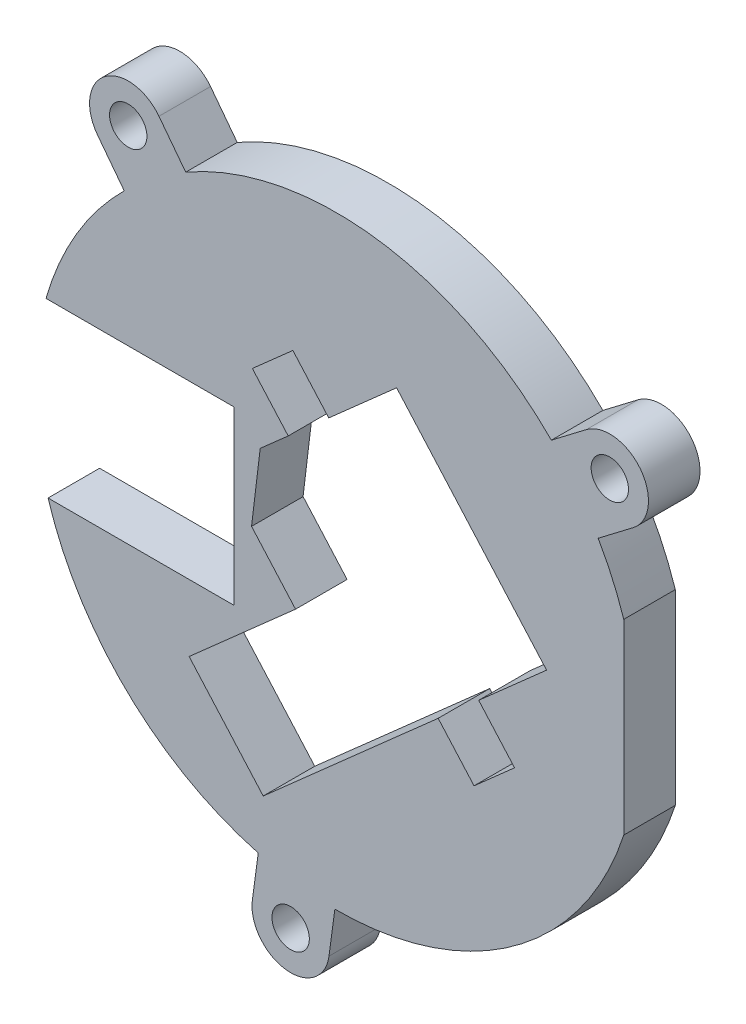
SolidWorks part; units mm, degrees
ref_plane "Front Plane" through (0, 0, 0) normal (0, 0, 1) x (1, 0, 0)
ref_plane "Top Plane" through (0, 0, 0) normal (0, 1, 0) x (1, 0, 0)
ref_plane "Right Plane" through (0, 0, 0) normal (1, 0, 0) x (0, 0, -1)
sketch "Sketch1" plane through (0, 0, 0) normal (0, 0, 1) x (1, 0, 0)
  line L0 (-21.141, 18.2245) -> (20.1141, 18.2245) construction
  line L1 (-4.8006, 1.8415) -> (-4.8006, -3.0861)
  line L2 (-4.8006, -3.0861) -> (-8.9662, -3.0861)
  line L3 (-8.9662, -3.0861) -> (-8.9662, -5.3514)
  line L4 (-8.9662, -5.3514) -> (-6.5786, -5.3514)
  line L5 (-4.9806, 7.3918) -> (-2.5835, 9.5123)
  line L6 (-2.5835, 9.5123) -> (-0.463, 7.1152)
  line L7 (-4.9806, 7.3918) -> (-2.8601, 4.9947)
  line L8 (3.2088, 10.3632) -> (-4.5153, 3.5306)
  line L9 (12.0777, 0.3371) -> (4.3536, -6.4955)
  line L10 (-4.5153, 3.5306) -> (-5.0276, -0.7207)
  line L11 (-5.0276, -0.7207) -> (0.0716, -6.4852)
  line L12 (0.0716, -6.4852) -> (4.3536, -6.4955)
  line L13 (-2.478, -3.6029) -> (7.6432, 5.3502) construction
  line L14 (3.2088, 10.3632) -> (12.0777, 0.3371)
  line L15 (3.2088, 10.3632) -> (11.8761, 18.0302)
  line L16 (-9.2588, -8.622) -> (-4.7522, -4.6355) construction
  line L17 (-9.2588, -8.622) -> (-5.994, -12.3128) construction
  line L18 (-4.7522, -4.6355) -> (-1.4874, -8.3263) construction
  line L19 (-5.994, -12.3128) -> (-1.4874, -8.3263) construction
  line L20 (12.0777, 0.3371) -> (20.228, 7.5468)
  line L21 (-6.5786, -5.3514) -> (-6.5786, -5.8039)
  line L22 (-6.5786, -5.8039) -> (-14.0208, -5.8039)
  line L23 (-14.0208, -5.8039) -> (-14.0208, 4.5593)
  line L24 (-14.0208, 4.5593) -> (-6.5786, 4.5593)
  line L25 (-6.5786, 4.5593) -> (-6.5786, 3.9924)
  line L26 (-6.5786, 3.9924) -> (-8.9662, 3.9924)
  line L27 (-8.9662, 3.9924) -> (-8.9662, 1.8415)
  line L28 (-8.9662, 1.8415) -> (-4.8006, 1.8415)
  line L29 (8.4059, -2.9109) -> (10.5264, -5.308)
  line L30 (10.5264, -5.308) -> (8.1292, -7.4285)
  line L31 (8.1292, -7.4285) -> (6.0088, -5.0313)
  line L32 (-4.7522, -4.6355) -> (-2.9639, -3.0536) construction
  line L33 (-1.4874, -8.3263) -> (0.5926, -6.4864) construction
  line L34 (-5.4555, -12.9216) -> (-0.9489, -8.9351)
  line L35 (-8.7203, -9.2308) -> (-4.2137, -5.2443)
  line L36 (-8.7203, -9.2308) -> (-5.4555, -12.9216)
  line L37 (-0.9489, -8.9351) -> (1.816, -6.4894)
  line L38 (-4.2137, -5.2443) -> (-2.4254, -3.6624)
  arc A0 (-15.2315, -0.5079) -> (3.302, 14.878) centre (0, 0) ccw construction
  circle A1 centre (0, 0) radius 21.59 construction
  circle A2 centre (0, 0) radius 21.59
  circle A3 centre (0, -18.415) radius 1.4224 construction
  circle A4 centre (0, 18.415) radius 1.4224 construction
  circle A5 centre (0, -18.415) radius 1.4224
  circle A6 centre (0, 18.415) radius 1.4224
  circle A7 centre (0, 0) radius 15.24
  dimension "D3" = 30.48
  dimension "D1" = 33.4645
  dimension "D2" = 20.0406
  dimension "D4" = 4.9276
  dimension "D5" = 2.7178
  dimension "D6" = 8.7122
  dimension "D7" = 7.8613
  dimension "D8" = 2.7178
  dimension "D9" = 3.2004
  dimension "D10" = 13.3858
  dimension "D11" = 3.1623
  dimension "D12" = 10.3124
  dimension "D13" = 8.6106
  dimension "D14" = 7.6962
  dimension "D15" = 6.0168
  dimension "D16" = 2.3876
  dimension "D17" = 4.9276
  dimension "D18" = 22.86
  dimension "D19" = 7.4422
  dimension "D20" = 5.0546
  dimension "D21" = 13.6652
  dimension "D22" = 29.2608
  dimension "D23" = 0.8128
extrude "Boss-Extrude1" add sketch "Sketch1" along normal blind 3.048 contours L15 A7 L20 L9 L29 L30 L31 L12 L33 L19 L17 L16 L32 L11 L1 L2 L3 L4 L21 L22 L23 L24 L25 L26 L27 L28 L10 L8 L7 L5 L6 | L28 L27 L26 L25 L24 L23 L22 L21 L4 L3 L2 L1 L11 L10 | A7 L15 A2 L20 A6 A5 region at (-6.8834, 2.2726, 0) region at (-10.1343, -0.6067, 0) region at (-13.5004, -8.3055, 0)
sketch "Sketch2" plane through (0, 0, 3.048) normal (0, 0, 1) x (1, 0, 0)
  line L0 (-5.0276, 2.3876) -> (-5.0276, -2.794)
  line L1 (-5.0276, 2.3876) -> (-10.4871, 2.3876)
  line L2 (-10.4871, 2.3876) -> (-10.4871, 3.8608)
  line L3 (-10.4871, 3.8608) -> (-7.085, 3.8608)
  line L4 (-7.085, 3.8608) -> (-7.085, 4.8768)
  line L5 (-7.085, 4.8768) -> (-14.4764, 4.8768)
  line L6 (-14.4764, 4.8768) -> (-14.4764, -5.2832)
  line L7 (-14.4764, -5.2832) -> (-7.085, -5.2832)
  line L8 (-7.085, -5.2832) -> (-7.085, -4.2672)
  line L9 (-7.085, -4.2672) -> (-10.4871, -4.2672)
  line L10 (-10.4871, -4.2672) -> (-10.4871, -2.794)
  line L11 (-10.4871, -2.794) -> (-5.0276, -2.794)
  line L12 (-5.0276, 2.3876) -> (-4.653, 2.3876)
  line L13 (-4.5153, 3.5306) -> (-5.0276, -0.7207) construction
  line L14 (-5.0276, -2.794) -> (-3.1935, -2.794)
  line L15 (-5.0276, -0.7207) -> (-2.4254, -3.6624) construction
  line L16 (-7.085, 3.8608) -> (-7.085, -4.2672)
  line L17 (-14.4764, 4.8768) -> (-21.032, 4.8768)
  line L18 (-14.4764, -5.2832) -> (-20.9336, -5.2832)
  arc A0 (11.8761, 18.0302) -> (20.228, 7.5468) centre (0, 0) ccw construction
  arc M2 (11.8761, 18.0302) -> (20.228, 7.5468) centre (0, 0) ccw
  dimension "D1" = 9.4488
  dimension "D2" = 7.3914
  dimension "D3" = 10.16
  dimension "D4" = 1.016
  dimension "D5" = 5.1816
  dimension "D6" = 5.4596
  dimension "D7" = 1.4732
  dimension "D8" = 1.143
extrude "Cut-Extrude3" cut sketch "Sketch2" against normal through all contours L10 L11 L0 L1 L2 L3 L4 L5 L6 L7 L8 L9 | L16 L3 L2 L1 | L16 L11 L10 L9 | L18 L6 L17 M2 region at (-11.0879, -0.2032, 3.048) region at (-8.7861, 3.1242, 3.048) region at (-8.7861, -3.5306, 3.048) region at (-17.9346, -0.1913, 3.048)
sketch "Sketch3" plane through (0, 0, 0) normal (0, 0, -1) x (-1, 0, 0)
  line L0 (-20.8712, -5.5245) -> (-16.9841, -5.5245)
  line L1 (-16.9841, -5.5245) -> (-20.8712, -5.5245) construction
  line L2 (-16.9841, -5.5245) -> (-16.9841, 4.6772)
  line L3 (-8.4059, -2.9109) -> (-20.228, 7.5468) construction
  line L4 (-16.9841, 5.5245) -> (-16.9841, -5.5245) construction
  line L5 (-16.9841, 4.6772) -> (-20.228, 7.5468)
  arc A0 (-20.228, 7.5468) -> (20.9336, -5.2832) centre (0, 0) ccw construction
  arc A1 (-20.228, 7.5468) -> (-20.8712, -5.5245) centre (0, 0) ccw
  arc A2 (-20.8712, -5.5245) -> (-20.8712, 5.5245) centre (0, 0) ccw construction
extrude "Cut-Extrude4" cut sketch "Sketch3" against normal through all
sketch "Sketch4" plane through (0, 0, 0) normal (0, 0, -1) x (-1, 0, 0)
  line L0 (-12.3201, -16.1591) -> (12.3201, 16.1591) construction
  line L1 (-13.8351, -15.0041) -> (10.8052, 17.3141)
  line L2 (-10.8052, -17.3141) -> (13.8351, 15.0041)
  line L3 (-16.1591, 12.3201) -> (16.1591, -12.3201) construction
  line L4 (-15.0041, 13.8351) -> (17.3141, -10.8052)
  line L5 (-17.3141, 10.8052) -> (15.0041, -13.8351)
  line L6 (-16.9841, 5.5245) -> (-16.9841, 4.6772)
  line L7 (-16.9841, 4.6772) -> (-12.4201, 0.64)
  line L8 (-8.4059, -2.9109) -> (-16.9841, 4.6772) construction
  line L9 (-12.4201, 0.64) -> (-3.5512, 10.6661)
  line L10 (0.463, 7.1152) -> (-11.8761, 18.0302) construction
  line L11 (-3.5512, 10.6661) -> (-8.9594, 15.4501)
  line L12 (5.0276, -0.7207) -> (2.4254, -3.6624) construction
  line L13 (0, 0) -> (2.7145, -20.1379) construction
  line L14 (1.8879, 0.2545) -> (4.6025, -19.8834)
  line L15 (-1.8879, -0.2545) -> (0.8266, -20.3924)
  line L16 (-16.1591, 12.3201) -> (12.3201, 16.1591) construction
  circle A0 centre (0, 0) radius 17.86
  arc A1 (-13.8351, -15.0041) -> (-10.8052, -17.3141) centre (-12.3201, -16.1591) ccw
  arc A2 (13.8351, 15.0041) -> (10.8052, 17.3141) centre (12.3201, 16.1591) ccw
  arc A3 (-15.0041, 13.8351) -> (-17.3141, 10.8052) centre (-16.1591, 12.3201) ccw
  arc A4 (15.0041, -13.8351) -> (17.3141, -10.8052) centre (16.1591, -12.3201) ccw
  circle A5 centre (12.3201, 16.1591) radius 1.1049
  circle A6 centre (16.1591, -12.3201) radius 1.1049
  circle A7 centre (-12.3201, -16.1591) radius 1.1049
  circle A8 centre (-16.1591, 12.3201) radius 1.1049
  arc A9 (1.8879, 0.2545) -> (-1.8879, -0.2545) centre (0, 0) ccw
  arc A10 (0.8266, -20.3924) -> (4.6025, -19.8834) centre (2.7145, -20.1379) ccw
  arc A11 (2.7145, -20.1379) -> (16.1591, -12.3201) centre (0, 0) ccw construction
  circle A12 centre (2.7145, -20.1379) radius 1.1049
  point P6 (0, 0)
  point P13 (0, 0)
  point P39 (1.3573, -10.0689)
  line M1 (-8.4059, -2.9109) -> (-16.9841, 4.6772)
  line M3 (-16.9841, -5.5245) -> (-20.8712, -5.5245)
  arc M4 (-20.8712, -5.5245) -> (20.9336, -5.2832) centre (0, 0) ccw
  line M5 (20.9336, -5.2832) -> (7.085, -5.2832)
  line M7 (7.085, 4.8768) -> (21.032, 4.8768)
  arc M8 (21.032, 4.8768) -> (-11.8761, 18.0302) centre (0, 0) ccw
  line M9 (-11.8761, 18.0302) -> (0.463, 7.1152)
  circle M24 centre (0, 18.415) radius 1.4224
  circle M25 centre (0, -18.415) radius 1.4224
  dimension "D1" = 3.81
  dimension "D2" = 3.81
  dimension "D3" = 13.97
extrude "Boss-Extrude2" add sketch "Sketch4" against normal up to vertex (3.048 mm away) contours A0 L4 L9 M9 | L4 A0 L5 L9 | L5 A0 L6 L9 M1 | L4 A3 L5 A0 A8 | A2 L1 A0 L2 A5 M8 | A0 M24 | A0 M25 | A0 L15 M25 | L15 A0 M25 | A10 M4 | A2 M8 region at (13.4131, 4.8762, 0) region at (10.9588, 8.3691, 0) region at (16.2523, 10.0852, 0) region at (0.2829, -17.4804, 0) region at (-2.9174, -21.6425, 0) region at (8.1323, 11.4955, 0) region at (-0.7535, -17.5272, 0) region at (-0.9598, -18.5708, 0) region at (-10.0849, 16.2525, 0) region at (0, 17.4932, 0) region at (-13.2407, 17.3665, 0) up to point (10.5264, -5.308, 3.048)
extrude "Cut-Extrude5" cut sketch "Sketch4<3>" against normal through all contours A4 L5 A0 L2 A1 M25 M4 | A4 A0 L4 M4 M5 | A1 L1 A0 M3 M4 | A7 | A6 | A5 | A2 L2 A0 M7 M8 | A2 A0 L1 M8 M9 M24 | L1 A1 L2 A0 A7 M4 | A10 A4 L5 A0 L14 M4 | A4 L4 A0 L5 A6 M4 | A12 region at (16.6582, -10.306, 0) region at (13.002, -14.0284, 0) region at (5.4053, -18.8788, 0) region at (-9.8123, -16.8747, 0) region at (-5.4955, 17.2518, 0) region at (-15.6105, -14.0703, 0) region at (-16.798, 10.0037, 0) region at (-18.1332, -7.9591, 0) region at (-12.3201, 16.1591, 0) region at (-16.1591, -12.3201, 0) region at (12.3201, -16.1591, 0) region at (-2.7145, -20.1379, 0)
sketch "Sketch4<3>" plane through (0, 0, 0) normal (0, 0, -1) x (-1, 0, 0) same geometry as "Sketch4"
sketch "Sketch5" plane through (0, 0, 3.048) normal (0, 0, 1) x (1, 0, 0)
  line L0 (4.3536, -6.4955) -> (-4.3384, -14.1843)
  line L1 (-4.3384, -14.1843) -> (-5.4555, -12.9216)
  line L2 (-8.7203, -9.2308) -> (-5.4555, -12.9216) construction
  line L3 (6.0088, -5.0313) -> (4.3536, -6.4955) construction
  line L4 (-5.4555, -12.9216) -> (1.816, -6.4894)
  line L5 (1.816, -6.4894) -> (4.3536, -6.4955)
extrude "Cut-Extrude10" cut sketch "Sketch5" against normal through all
sketch "Sketch6" plane through (0, 0, 3.048) normal (0, 0, 1) x (1, 0, 0)
  line L0 (17.3141, 10.8052) -> (15.2768, 9.2519) construction
  line L1 (15.0041, 13.8351) -> (12.9668, 12.2818) construction
  line L2 (17.3141, 10.8052) -> (15.2768, 9.2519)
  line L3 (15.0041, 13.8351) -> (12.9668, 12.2818)
  line L4 (17.5451, 10.5023) -> (15.472, 8.9216)
  line L5 (14.7731, 14.138) -> (12.7, 12.5574)
  line L23 (-4.9801, -19.8325) -> (-4.6378, -17.2935)
  line L24 (-0.1068, -17.9043) -> (-0.449, -20.4433)
  line L25 (-4.9801, -19.8325) -> (-4.6318, -17.2489)
  line L26 (-0.1008, -17.8597) -> (-0.449, -20.4433)
  line L29 (14.7731, 14.138) -> (12.7358, 12.5847) construction
  line L30 (17.5451, 10.5023) -> (15.5078, 8.9489) construction
  line L31 (-14.138, 14.7731) -> (-12.5847, 12.7358)
  line L32 (-8.9489, 15.5078) -> (-10.5023, 17.5451)
  line L33 (-14.138, 14.7731) -> (-12.5574, 12.7)
  line L34 (-8.9216, 15.472) -> (-10.5023, 17.5451)
  arc A0 (17.3141, 10.8052) -> (15.0041, 13.8351) centre (16.1591, 12.3201) ccw construction
  arc A1 (17.3141, 10.8052) -> (15.0041, 13.8351) centre (16.1591, 12.3201) ccw
  arc A2 (17.5451, 10.5023) -> (14.7731, 14.138) centre (16.1591, 12.3201) ccw
  arc A11 (-4.9801, -19.8325) -> (-0.449, -20.4433) centre (-2.7145, -20.1379) ccw
  arc A12 (-4.9801, -19.8325) -> (-0.449, -20.4433) centre (-2.7145, -20.1379) ccw
  circle A14 centre (0, 0) radius 17.86
  arc A15 (-10.5023, 17.5451) -> (-14.138, 14.7731) centre (-12.3201, 16.1591) ccw
  arc A16 (-10.5023, 17.5451) -> (-14.138, 14.7731) centre (-12.3201, 16.1591) ccw
  line M25 (-4.2602, -17.3444) -> (-4.6025, -19.8834)
  arc M26 (-4.6025, -19.8834) -> (-0.8266, -20.3924) centre (-2.7145, -20.1379) ccw
  line M27 (-0.8266, -20.3924) -> (-0.4844, -17.8534)
  arc M28 (-0.4844, -17.8534) -> (16.9841, -5.5245) centre (0, 0) ccw
  arc M30 (16.9841, 5.5245) -> (15.2768, 9.2519) centre (0, 0) ccw
  line M31 (15.2768, 9.2519) -> (17.3141, 10.8052)
  arc M32 (17.3141, 10.8052) -> (15.0041, 13.8351) centre (16.1591, 12.3201) ccw
  line M33 (15.0041, 13.8351) -> (12.9668, 12.2818)
  arc M34 (12.9668, 12.2818) -> (-9.2519, 15.2768) centre (0, 0) ccw
  line M35 (-9.2519, 15.2768) -> (-10.8052, 17.3141)
  arc M36 (-10.8052, 17.3141) -> (-13.8351, 15.0041) centre (-12.3201, 16.1591) ccw
  line M37 (-13.8351, 15.0041) -> (-12.2818, 12.9668)
  arc M38 (-12.2818, 12.9668) -> (-17.1812, 4.8768) centre (0, 0) ccw
  arc M42 (-17.0607, -5.2832) -> (-4.2602, -17.3444) centre (0, 0) ccw
  dimension "D1" = 0.381
  dimension "D2" = 0.381
  dimension "D3" = 0.381
extrude "Boss-Extrude3" add sketch "Sketch6" against normal up to vertex contours L34 A16 L33 M38 M37 M36 M35 M34 | L25 A12 L26 M28 M27 M26 M25 M42 | L4 A2 L5 M34 M33 M32 M31 M30 region at (17.7383, 13.5242, 3.048) region at (-9.1284, 15.4449, 3.048) region at (-0.1744, -17.8725, 3.048) up to point (8.4059, -2.9109, 0)
sketch "Sketch7" plane through (0, 0, 0) normal (0, 0, -1) x (-1, 0, 0)
  line L0 (7.085, 4.8768) -> (6.0563, 4.8768)
  line L1 (6.0563, 4.8768) -> (6.0563, -5.2832)
  line L2 (6.0563, -5.2832) -> (7.085, -5.2832)
  line L3 (5.0276, -0.7207) -> (7.085, -0.7207) construction
  line L4 (7.085, 4.8768) -> (7.085, -5.2832) construction
  line L5 (7.085, 4.8768) -> (7.085, -5.2832)
  point P11 (6.0563, -0.7207)
extrude "Cut-Extrude11" cut sketch "Sketch7" against normal through all
